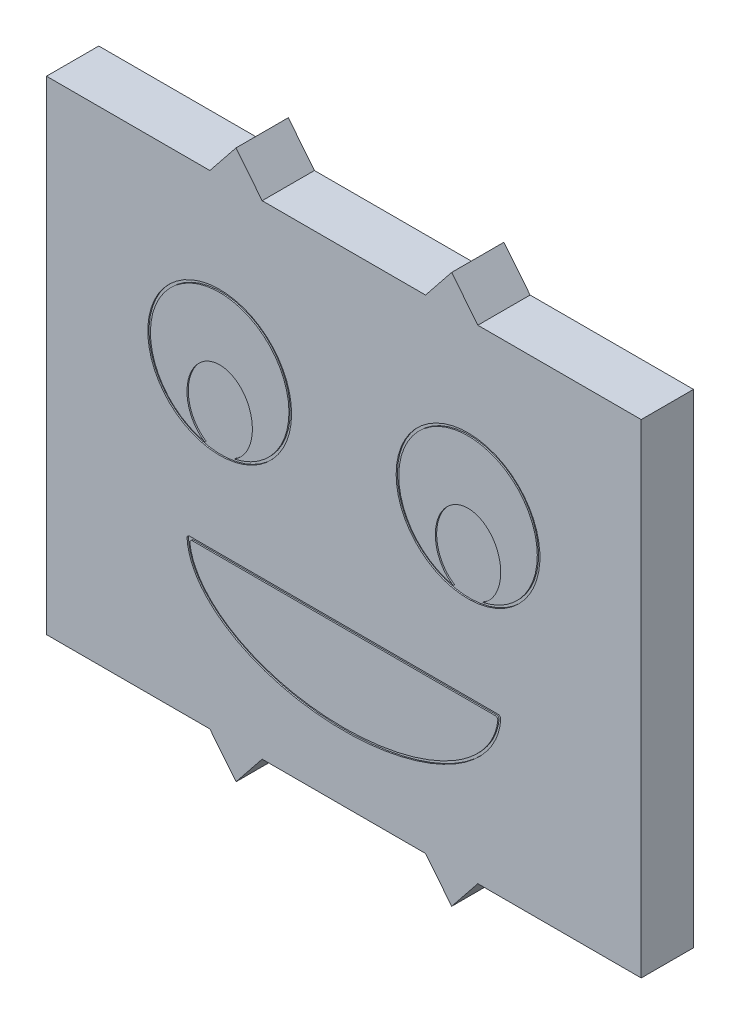
SolidWorks part; units mm, degrees
ref_plane "Front Plane" through (0, 0, 0) normal (0, 0, 1) x (1, 0, 0)
ref_plane "Top Plane" through (0, 0, 0) normal (0, 1, 0) x (1, 0, 0)
ref_plane "Right Plane" through (0, 0, 0) normal (1, 0, 0) x (0, 0, -1)
sketch "Sketch1" plane through (0, 0, 0) normal (0, 0, 1) x (1, 0, 0)
  line L0 (22.75, 37) -> (22.75, 14.7203) construction
  line L1 (0, 0) -> (45.5, 0)
  line L2 (0, 0) -> (0, 37)
  line L3 (0, 37) -> (45.5, 37)
  line L4 (45.5, 0) -> (45.5, 37)
  line L5 (12.5, 37) -> (14.5, 39.5)
  line L6 (14.5, 39.5) -> (16.5, 37)
  line L7 (31, 39.5) -> (29, 37)
  line L8 (33, 37) -> (31, 39.5)
  line L9 (0, 18.5) -> (57.9593, 18.5) construction
  line L10 (33, 0) -> (31, -2.5)
  line L11 (31, -2.5) -> (29, 0)
  line L12 (14.5, -2.5) -> (16.5, 0)
  line L13 (12.5, 0) -> (14.5, -2.5)
  point P9 (22.75, 37)
  point P16 (0, 18.5)
  point P17 (32, 38.25)
  point P18 (32, -1.25)
  dimension "D1" = 37
  dimension "D2" = 45.5
  dimension "D3" = 16.5
  dimension "D4" = 2.5
  dimension "D5" = 4
extrude "Basis" add sketch "Sketch1" along normal blind 4 contours L1 L4 L3 L2 | L6 L5 L3 | L3 L8 L7 | L1 L13 L12 | L11 L10 L1 region at (22.75, 18.5, 0) region at (14.5, -0.8333, 0) region at (14.5, 37.8333, 0) region at (31, -0.8333, 0) region at (31, 37.8333, 0)
sketch "Sketch3" [suppressed] plane through (0, 0, 4) normal (0, 0, 1) x (1, 0, 0)
  line L0 (22.75, 37) -> (22.75, 0) construction
  line L1 (16.5, 37) -> (29, 37) construction
  line L2 (16.5, 0) -> (29, 0) construction
  line L3 (0, 37) -> (12.5, 37) construction
  circle A0 centre (9.8, 25.6) radius 7.95
  circle A1 centre (35.7, 25.6) radius 7.95
  dimension "D3" = 15.9
  dimension "D1" = 11.4
  dimension "D2" = 25.9
extrude "HR04 gat " [suppressed] cut sketch "Sketch3" against normal up to surface (4 mm away)
sketch "Sketch4" [suppressed] plane through (0, 0, 4) normal (0, 0, 1) x (1, 0, 0)
  line L0 (7.7992, 12.9938) -> (37.7008, 12.9938) construction
  line L1 (16.5, 37) -> (29, 37) construction
  text T0 "AFSTAND SENSOR" font "Yu Gothic UI Semilight" height 3.5
  point P5 (22.75, 12.9938)
  point P8 (22.75, 37)
extrude "Afstand sensor" [suppressed] cut sketch "Sketch4" against normal blind 0.2
sketch "Sketch6" plane through (0, 0, 4) normal (0, 0, 1) x (1, 0, 0)
  line L4 (16.5, 37) -> (29, 37) construction
  point P0 (22.75, 31.8)
  point P3 (22.75, 37)
  line B0 (9.1, 31.8) -> (36.4, 31.8)
  line B1 (9.1, 31.8) -> (9.1, 16.3191)
  line B2 (9.1, 16.3191) -> (36.4, 16.3191)
  line B3 (36.4, 31.8) -> (36.4, 16.3191)
  circle B4 centre (11.1, 34.0981) radius 1.5
  circle B5 centre (34.4, 34.0981) radius 1.5
  circle B6 centre (34.4, 10.2981) radius 1.5
  circle B7 centre (11.1, 10.2981) radius 1.5
  dimension "D1" = 5.2
sketch_block_instance "Block1-1"
sketch_block "Block1" parameters "D1"=3, "D2"=3, "D3"=3, "D4"=3
extrude "Cut-Extrude5" [suppressed] cut sketch "Sketch6" against normal up to surface (4 mm away)
sketch "Sketch7" [suppressed] plane through (0, 0, 4) normal (0, 0, 1) x (1, 0, 0)
  line L0 (-2.0092, 11.0348) -> (47.5092, 11.0348) construction
  line L1 (16.5, 37) -> (29, 37) construction
  text T0 "oled scherm " font "Yu Gothic UI Semilight" height 3.5
  point P4 (22.75, 37)
  point P5 (22.75, 11.0348)
extrude "Cut-Extrude6" [suppressed] cut sketch "Sketch7" against normal blind 0.2
sketch "Sketch9" [suppressed] plane through (0, 0, 4) normal (0, 0, 1) x (1, 0, 0)
  line L0 (15.4564, 12.6867) -> (24.4394, 12.6867) construction
  text T0 "V0.2"
extrude "Cut-Extrude8" [suppressed] cut sketch "Sketch9" against normal blind 0.2
sketch "Sketch10" plane through (0, 0, 4) normal (0, 0, 1) x (1, 0, 0)
  line L0 (10.75, 12) -> (34.75, 12)
  line L1 (16.5, 37) -> (29, 37) construction
  line L2 (16.5, 0) -> (29, 0) construction
  line L3 (10.9552, 11.8) -> (34.5448, 11.8)
  circle A0 centre (13.25, 24) radius 5.5
  circle A1 centre (13.25, 24) radius 5.3
  ellipse E0 centre (13.25, 21.5) end of major axis (13.25, 18.5) minor radius 2.5
  ellipse E1 centre (22.75, 12) end of major axis (10.75, 12) minor radius 7 (10.75, 12) -> (34.75, 12) ccw
  spline S0 degree 1 poles (10.9552, 11.8) (34.5448, 11.8) knots 0 0 1 1 construction
  spline S1 degree 3 poles (34.5448, 11.8) (34.5225, 11.3662) (34.3376, 10.5228) (33.4058, 8.8675) (31.2201, 7.0302) (27.3266, 5.5471) (22.75, 5.0264) (18.1734, 5.5471) (14.2799, 7.0302) (12.0942, 8.8675) (11.1624, 10.5228) (10.9775, 11.3662) (10.9552, 11.8) knots 3.171639 3.171639 3.171639 3.171639 3.364233 3.556826 3.942014 4.327201 4.712389 5.097577 5.482764 5.867952 6.060545 6.253139 6.253139 6.253139 6.253139
  point P6 (22.75, 37)
  point P20 (0, 0)
  point P21 (22.75, 0)
  dimension "D2" = 11
  dimension "D10" = 0.2
  dimension "D1" = 13
  dimension "D3" = 9.5
  dimension "D4" = 24
  dimension "D5" = 7
  dimension "D6" = 12
  dimension "D7" = 5
  dimension "D8" = 6
  dimension "D9" = 2.5
  dimension "D11" = 0.2
extrude "Cut-Extrude10" cut sketch "Sketch10" against normal blind 0.1 contours L0 E1 region at (22.75, 11.975, 4)
extrude "Cut-Extrude14" cut sketch "Sketch10<6>" against normal blind 0.1 contours A1 E0 region at (13.25, 21.5374, 4)
sketch "Sketch10<6>" plane through (0, 0, 4) normal (0, 0, 1) x (1, 0, 0) same geometry as "Sketch10"
ref_plane "Plane1" through (22.75, 0, 0) normal (-1, 0, 0) x (0, 0, 1)
extrude "Cut-Extrude16" cut sketch "Sketch10<9>" against normal blind 0.1 contours A0 | A1
sketch "Sketch10<9>" plane through (0, 0, 4) normal (0, 0, 1) x (1, 0, 0) same geometry as "Sketch10"
mirror "Mirror1" about plane through (22.75, 0, 0) normal (-1, 0, 0) of "Cut-Extrude14", "Cut-Extrude16"
fillet "Fillet1" radius 0.2 4 edges at (34.5448, 11.8, 3.95) (34.75, 12, 3.95) (10.9552, 11.8, 3.95) (10.75, 12, 3.95)
